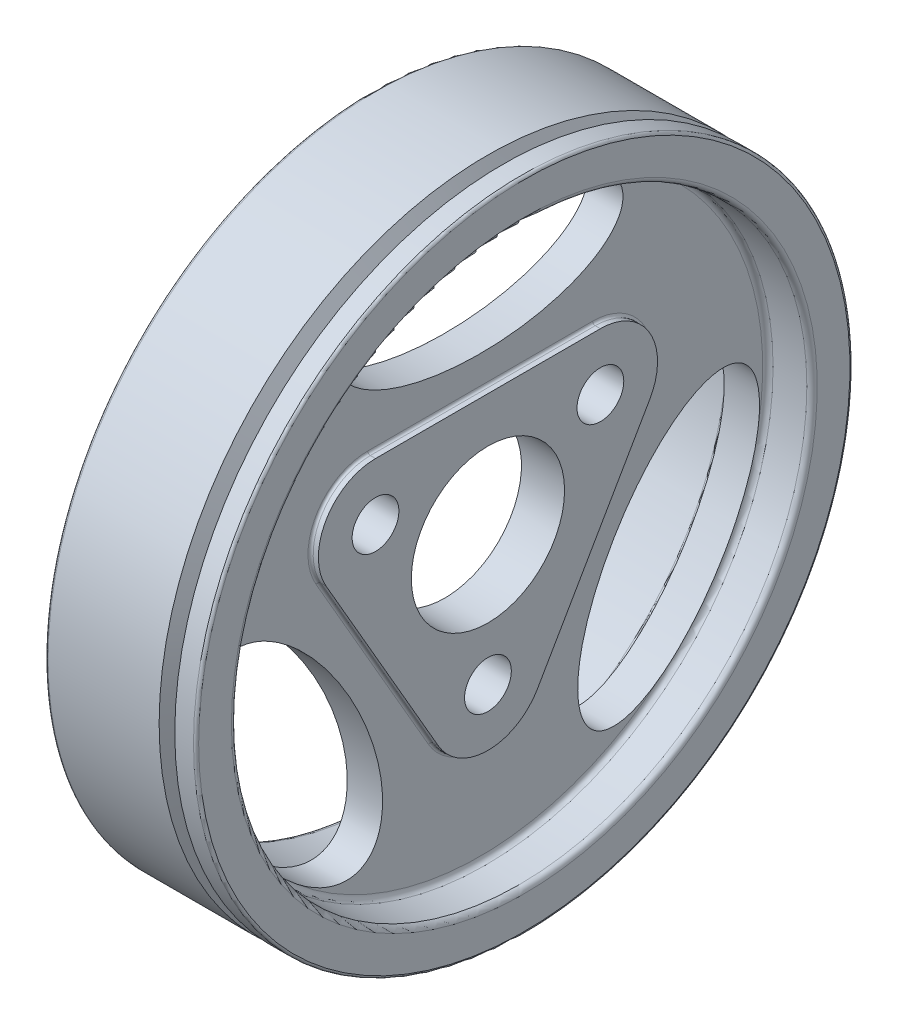
SolidWorks part; units mm, degrees
material "AISI 1010 Сталь, горяченакатанная полоса"
ref_plane "Спереди" through (0, 0, 0) normal (0, 0, 1) x (1, 0, 0)
ref_plane "Сверху" through (0, 0, 0) normal (0, 1, 0) x (1, 0, 0)
ref_plane "Справа" through (0, 0, 0) normal (1, 0, 0) x (0, 0, -1)
sketch "Эскиз1" plane through (0, 0, 0) normal (0, 0, 1) x (1, 0, 0)
  line L0 (13.7, 14.75) -> (20.5, 14.75)
  line L1 (20.5, 14.75) -> (20.5, 55.4)
  line L2 (20.5, 55.4) -> (29, 55.4)
  line L3 (29, 55.4) -> (29, 63.2)
  line L4 (29, 63.2) -> (0, 63.2)
  line L5 (0, 63.2) -> (0, 55.4)
  line L6 (0, 55.4) -> (13.7, 55.4)
  line L7 (13.7, 55.4) -> (13.7, 14.75)
  line L8 (-584.1514, 0) -> (28623.4206, 0) construction
  dimension "D1" = 29
  dimension "D2" = 126.4
  dimension "D3" = 29.5
  dimension "D4" = 7.8
  dimension "D5" = 8.5
  dimension "D6" = 13.7
revolve "Повернуть1" add sketch "Эскиз1" angle 360 about L8
fillet "Скругление1" radius 1 4 edges at (0, 0, 55.4) (13.7, 0, 55.4) (20.5, 0, 55.4) (29, 0, 55.4)
fillet "Скругление2" radius 0.5 2 edges at (29, 0, 63.2) (0, 0, 63.2)
sketch "Эскиз2" plane through (0, 0, 0) normal (0, 1, 0) x (1, 0, 0)
  line L0 (3.8285, 63.7) -> (5.6071, 60.4243) construction
  line L1 (5.6071, 60.4243) -> (7.3857, 63.7) construction
  line L2 (7.3857, 63.7) -> (9.1643, 60.4243) construction
  line L3 (9.1643, 60.4243) -> (10.9428, 63.7) construction
  line L4 (10.9428, 63.7) -> (12.7214, 60.4243) construction
  line L5 (12.7214, 60.4243) -> (14.5, 63.7) construction
  line L6 (14.5, 63.7) -> (16.2786, 60.4243) construction
  line L7 (16.2786, 60.4243) -> (18.0572, 63.7) construction
  line L8 (18.0572, 63.7) -> (19.8357, 60.4243) construction
  line L9 (19.8357, 60.4243) -> (21.6143, 63.7) construction
  line L10 (21.6143, 63.7) -> (23.3929, 60.4243) construction
  line L11 (23.3929, 60.4243) -> (25.1715, 63.7) construction
  line L12 (3.8285, 63.7) -> (3.8285, 63.2) construction
  line L13 (3.8285, 63.2) -> (25.1715, 63.2) construction
  line L14 (25.1715, 63.2) -> (25.1715, 63.7) construction
  line L15 (3.8285, 63.7) -> (25.1715, 63.7) construction
  line L16 (24.9, 63.2) -> (23.3929, 60.4243)
  line L17 (23.3929, 60.4243) -> (21.8858, 63.2)
  line L18 (28.5, 63.2) -> (0.5, 63.2) construction
  line L19 (28.5, 63.2) -> (0.5, 63.2) construction
  line L20 (21.8858, 63.2) -> (24.9, 63.2)
  line L21 (28.5, 63.2) -> (0.5, 63.2) construction
  line L22 (0, 62.7) -> (0, -62.7) construction
  line L23 (29, -62.7) -> (29, 62.7) construction
  point P21 (24.9, 63.2)
  point P22 (4.1, 63.2)
  dimension "D4" = 57
  dimension "D5" = 0.5
  dimension "D3" = 4.1
  dimension "D6" = 3.5572
  dimension "D2" = 4.1
  dimension "D7" = 21.343
revolve "Повернуть2" add sketch "Эскиз2" angle 360 about L8
combine bodies "Соединить1" operation type subtract main body 103 bodies to subtract 104
sketch "Эскиз3" plane through (13.7, 0, 0) normal (-1, 0, 0) x (0, 0, 1)
  line L0 (0, -1000) -> (0, 49000) construction
  circle A0 centre (0, 0) radius 54.4 construction
  circle A1 centre (0, -25) radius 4.5
  circle A2 centre (-21.6506, 12.5) radius 4.5
  circle A3 centre (21.6506, 12.5) radius 4.5
  ellipse E0 centre (0, 41.9) end of major axis (27.5, 41.9) minor radius 12.5
  ellipse E1 centre (36.2865, -20.95) end of major axis (22.5365, -44.7657) minor radius 12.5
  ellipse E2 centre (-36.2865, -20.95) end of major axis (-50.0365, 2.8657) minor radius 12.5
  point P32 (0, 0)
  dimension "D4" = 9
  dimension "D1" = 55
  dimension "D2" = 25
  dimension "D3" = 25
  dimension "D5" = 3
extrude "Вырез-Вытянуть1" cut sketch "Эскиз3" against normal through all both and the other way through all
sketch "Эскиз4" plane through (20.5, 0, 0) normal (1, 0, 0) x (0, 0, -1)
  line L0 (-21.6506, 23.5) -> (21.6506, 23.5)
  line L1 (31.1769, 7) -> (9.5263, -30.5)
  line L2 (-31.1769, 7) -> (-9.5263, -30.5)
  arc A1 (31.1769, 7) -> (21.6506, 23.5) centre (21.6506, 12.5) ccw
  arc A2 (-9.5263, -30.5) -> (9.5263, -30.5) centre (0, -25) ccw
  arc A3 (-21.6506, 23.5) -> (-31.1769, 7) centre (-21.6506, 12.5) ccw
  circle A4 centre (21.6506, 12.5) radius 4.5 construction
  circle A5 centre (0, -25) radius 4.5 construction
  circle A6 centre (-21.6506, 12.5) radius 4.5 construction
  circle A7 centre (0, 0) radius 14.75 construction
  circle A8 centre (21.6506, 12.5) radius 4.5
  circle A9 centre (0, -25) radius 4.5
  circle A10 centre (-21.6506, 12.5) radius 4.5
  circle A11 centre (0, 0) radius 14.75
  dimension "D1" = 6.5
extrude "Бобышка-Вытянуть1" add sketch "Эскиз4" along normal blind 1.5
fillet "Скругление3" radius 0.5 6 edges at (20.5, 18, -31.1769) (20.5, -11.75, -20.3516) (20.5, -36, 0) (20.5, -11.75, 20.3516) (20.5, 18, 31.1769) (20.5, 23.5, 0)
sketch "Эскиз5" plane through (13.7, 0, 0) normal (-1, 0, 0) x (0, 0, 1)
  circle A0 centre (-21.6506, 12.5) radius 8
  circle A1 centre (21.6506, 12.5) radius 8
  circle A2 centre (0, -25) radius 8
  circle A3 centre (0, -25) radius 4.5 construction
  dimension "D1" = 16
extrude "Вырез-Вытянуть2" cut sketch "Эскиз5" against normal blind 1
ref_plane "Плоскость1" through (4.1, 0, 0) normal (1, 0, 0) x (0, 0, -1)
ref_plane "Плоскость2" through (24.9, 0, 0) normal (1, 0, 0) x (0, 0, -1)
ref_plane "Середина шкива" through (14.5, 0, 0) normal (1, 0, 0) x (0, 0, -1)
equation "\"D2@Эскиз2\"=\"D3@Эскиз2\""
